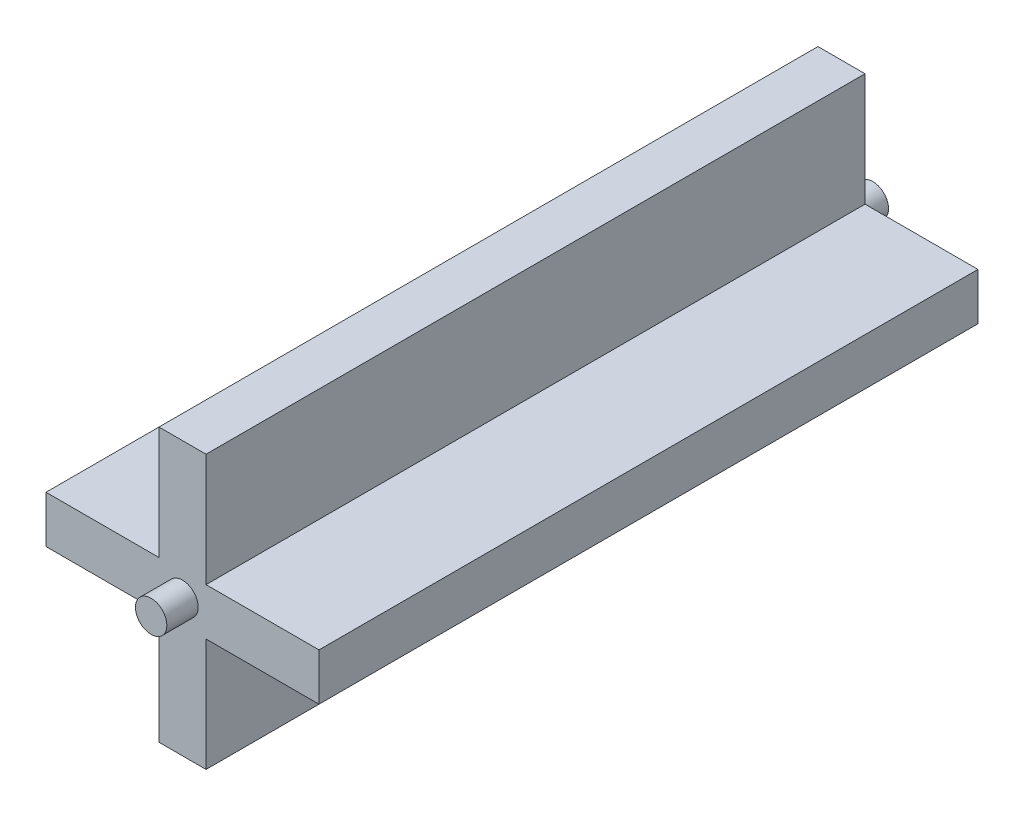
SolidWorks part; units mm, degrees
ref_plane "Front Plane" through (0, 0, 0) normal (0, 0, 1) x (1, 0, 0)
ref_plane "Top Plane" through (0, 0, 0) normal (0, 1, 0) x (1, 0, 0)
ref_plane "Right Plane" through (0, 0, 0) normal (1, 0, 0) x (0, 0, -1)
sketch "Sketch1" plane through (0, 0, 0) normal (0, 0, 1) x (1, 0, 0)
  line L0 (-7.5, 7.5) -> (-7.5, 43.5)
  line L6 (0, -55) -> (0, 55) construction
  line L7 (55, 0) -> (-55, 0) construction
  line L14 (-7.5, 43.5) -> (7.5, 43.5)
  line L15 (7.5, 43.5) -> (7.5, 7.5)
  line L16 (7.5, 7.5) -> (43.5, 7.5)
  line L17 (43.5, 7.5) -> (43.5, -7.5)
  line L18 (43.5, -7.5) -> (7.5, -7.5)
  line L19 (7.5, -7.5) -> (7.5, -43.5)
  line L20 (7.5, -43.5) -> (-7.5, -43.5)
  line L21 (-7.5, -43.5) -> (-7.5, -7.5)
  line L22 (-7.5, -7.5) -> (-43.5, -7.5)
  line L23 (-43.5, -7.5) -> (-43.5, 7.5)
  line L24 (-43.5, 7.5) -> (-7.5, 7.5)
  point P0 (0, 0)
  point P1 (0, 43.5)
  point P4 (43.5, 0)
  point P5 (0, 0)
  point P9 (-43.5, 0)
  dimension "D1" = 36
  dimension "D2" = 15
extrude "Boss-Extrude1" add sketch "Sketch1" along normal mid plane 210
sketch "Sketch2" plane through (0, 0, 105) normal (0, 0, 1) x (1, 0, 0)
  circle A0 centre (0, 0) radius 5
  dimension "D1" = 10
extrude "Boss-Extrude2" add sketch "Sketch2" along normal blind 10 contours A0
mirror "Mirror1" about plane through (0, 0, 0) normal (0, 0, 1) of "Boss-Extrude2"
